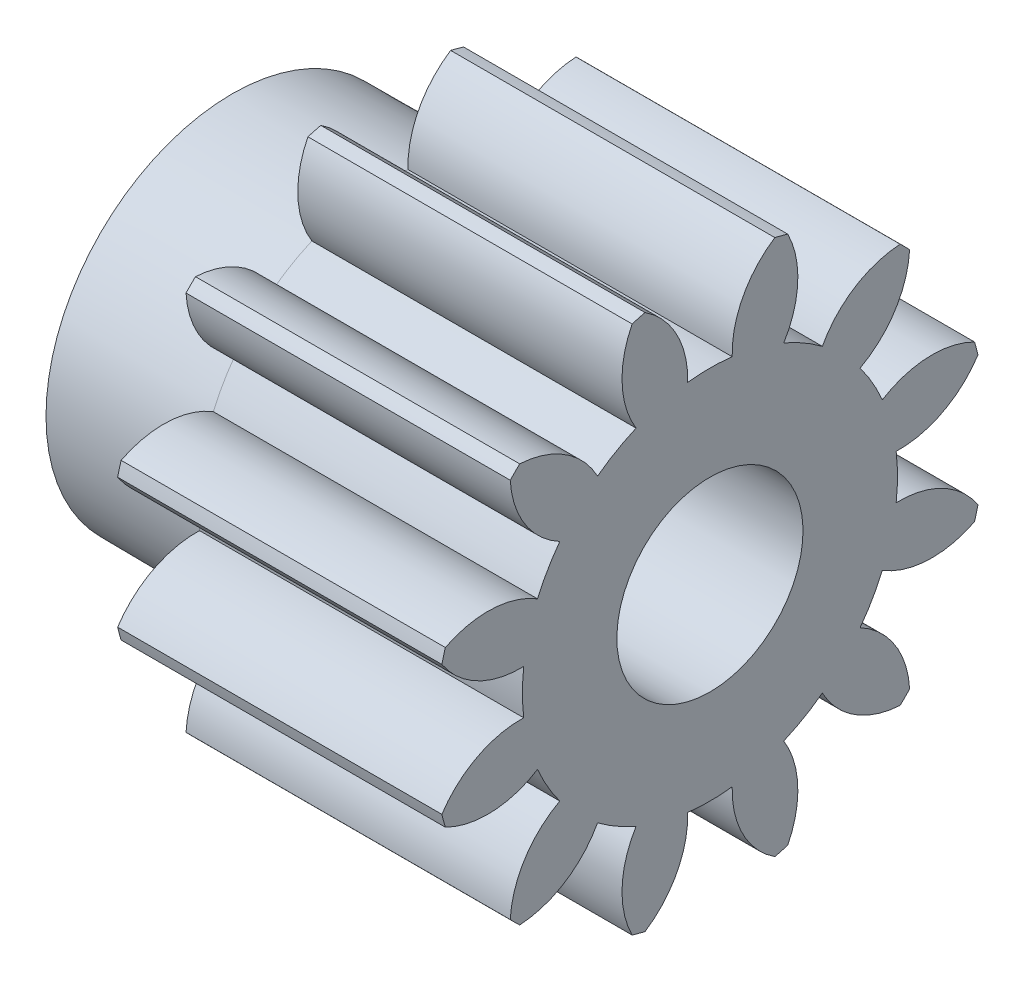
SolidWorks part; units mm, degrees
material "ABS"
ref_plane "Plane1" through (0, 0, 0) normal (0, 0, 1) x (1, 0, 0)
ref_plane "Plane2" through (0, 0, 0) normal (0, 1, 0) x (1, 0, 0)
ref_plane "Plane3" through (0, 0, 0) normal (1, 0, 0) x (0, 0, -1)
sketch "HoldingSke" plane through (0, 0, 0) normal (0, 1, 0) x (1, 0, 0)
  line L0 (0, 0) -> (496.899, -105.6191)
  line L1 (-15, 0) -> (100, 0) construction
  line L2 (0, 0) -> (-2.1039, 2.3779)
  line L3 (0, 0) -> (-11.863, 4.5341)
  line L4 (0, 0) -> (8.4473, 1.7955)
  line L5 (0, 0) -> (-47.5972, -17.7524)
  line L6 (0, 0) -> (-10.5278, -7.1032)
  line L7 (-2.1039, 2.3779) -> (8.8308, 51.9871)
  line L8 (-76.2, 54.61) -> (-69.596, 54.61)
  line L9 (-71.009, 38.7566) -> (-53.1078, 45.2721)
  line L10 (-76.2, 71.12) -> (104.1128, 71.12)
  line L11 (0, 0) -> (-12.7, 0)
  line L12 (-76.2, 101.6) -> (-76.1492, 101.6)
  line L13 (24.9733, 27.94) -> (52.9518, 28.4284)
  line L14 (24.9733, 27.94) -> (25.0241, 27.9398)
  line L15 (24.9733, 27.94) -> (100.4021, 29.52)
  circle A0 centre (0, 0) radius 3.175
  circle A1 centre (0, 0) radius 6.0452
  circle A2 centre (0, 0) radius 38.1
  circle A3 centre (0, 0) radius 3.175
  dimension "Num_teeth" = 12
  dimension "H" = 19.05
  dimension "Pitch_radius" = 180.3128
  dimension "Width" = 12.7
  dimension "Thickness" = 12.7
sketch "BasProSke" plane through (0, 0, 0) normal (0, 1, 0) x (1, 0, 0)
  line L0 (-10, 0) -> (60, 0) construction
  line L1 (0, 0) -> (0, 8.89)
  line L2 (0, 0) -> (12.7, 0)
  line L3 (12.7, 0) -> (12.7, 8.89)
  line L4 (12.7, 8.89) -> (0, 8.89)
  dimension "Thickness" = 12.7
  dimension "Diameter" = 17.78
revolve "Base-Revolve" add sketch "BasProSke" angle 360 about L0
sketch "TooCutSke" plane through (0, 0, 0) normal (1, 0, 0) x (0, 0, -1)
  line L1 (0, 0) -> (0, 107) construction
  line L2 (0, 0) -> (-1.0834, 7.5426) construction
  line L3 (0, 0) -> (-3.9164, 14.6164) construction
  line L4 (-1.0834, 7.5426) -> (-1.9582, 7.3082) construction
  arc A0 (0.7171, 6.0025) -> (-0.7171, 6.0025) centre (0, 0) ccw
  arc A1 (2.1216, 8.6593) -> (-2.1216, 8.6593) centre (0, 0) ccw
  circle A2 centre (0, 0) radius 7.62 construction
  circle A3 centre (0, 0) radius 7.1605 construction
  arc A4 (-0.7171, 6.0025) -> (-2.1216, 8.6593) centre (-3.7638, 6.0915) ccw
  arc A5 (2.1216, 8.6593) -> (0.7171, 6.0025) centre (3.7638, 6.0915) ccw
extrude "ToothCut" cut sketch "TooCutSke" along normal through all
fillet "Breaks" [suppressed] radius 0.0254 tangent propagation no
fillet "RootFillets" [suppressed] radius 0.3048
pattern_circular "TeethCuts" count 12 every 30 about axis through (-10, 0, 0) along (1, 0, 0) of "ToothCut", "RootFillets", "Breaks"
sketch "HubNeaOneSke" plane through (0, 0, 0) normal (-1, 0, 0) x (0, 0, 1)
  circle A0 centre (0, 0) radius 6.0452
  dimension "Diameter" = 12.0904
extrude "HubNearOne" [suppressed] add sketch "HubNeaOneSke" along normal blind 38.1001
sketch "HubNeaBotSke" plane through (0, 0, 0) normal (-1, 0, 0) x (0, 0, 1)
  circle A0 centre (0, 0) radius 6.0452
  dimension "Diameter" = 12.0904
extrude "HubNearBoth" [suppressed] add sketch "HubNeaBotSke" along normal blind 19.05
ref_plane "FarPln" through (12.7, 0, 0) normal (1, 0, 0) x (0, 0, -1)
sketch "HubFarSke" plane through (12.7, 0, 0) normal (1, 0, 0) x (0, 0, -1)
  circle A0 centre (0, 0) radius 6.0452
  dimension "Diameter" = 12.0904
extrude "HubFar" [suppressed] add sketch "HubFarSke" along normal blind 19.05
sketch "BorSke" plane through (0, 0, 0) normal (1, 0, 0) x (0, 0, -1)
  circle A0 centre (0, 0) radius 3
  dimension "D1" = 6
extrude "Bore" cut sketch "BorSke" along normal mid plane 101.6001
sketch "KeySke" plane through (0, 0, 0) normal (1, 0, 0) x (0, 0, -1)
  line L0 (-0.127, 0) -> (-0.127, 3.429)
  line L1 (-0.127, 3.429) -> (0.127, 3.429)
  line L2 (0.127, 3.429) -> (0.127, 0)
  line L3 (0, 0) -> (0, 34) construction
  line L4 (-0.127, 0) -> (0.127, 0)
  dimension "Width" = 0.254
extrude "Keyway" [suppressed] cut sketch "KeySke" along normal mid plane 101.6001
pattern_circular "Keyway2" [suppressed] count 2 every 90 about axis through (-10, 0, 0) along (1, 0, 0) reverse direction yes
sketch "Sketch1" plane through (0, 0, 0) normal (0, 0, 1) x (1, 0, 0)
  line L0 (0, 0) -> (-2.5422, 0) construction
  line L1 (0, -4) -> (-4.95, -4)
  line L2 (-4.95, -4) -> (-4.95, -6)
  line L3 (-4.95, -6) -> (0, -6.0452)
  line L4 (0, -6.0452) -> (0, -4)
  dimension "D1" = 2
  dimension "D2" = 4
  dimension "D3" = 4.95
revolve "Revolve1" add sketch "Sketch1" angle 360 about L0
sketch "Sketch2" plane through (0, 0, 0) normal (0, 0, 1) x (1, 0, 0)
  line L0 (12.7, -8.6403) -> (0, -8.6403) construction
  line L1 (12.7, 8.6403) -> (10.45, 8.6403)
  line L2 (12.7, 8.6403) -> (12.7, -8.6403)
  line L3 (12.7, -8.6403) -> (10.45, -8.6403)
  line L4 (10.45, 8.6403) -> (10.45, -8.6403)
  dimension "D1" = 2.25
extrude "Cut-Extrude1" cut sketch "Sketch2" against normal through all both and the other way through all
ref_axis "Axis1" through (-5.8156, 0, 0) along (1, 0, 0)
equation "' \"Pitch@HoldingSke\" = 4"
equation "' \"Num_teeth@HoldingSke\" = 12"
equation "' \"Ap@HoldingSke\" =  20"
equation "' \"Ap@HoldingSke\" = 20"
equation "' \"Width@HoldingSke\" = 0.5"
equation "' \"Hub_dia@HoldingSke\"= 1"
equation "' \"Hub_dia@HoldingSke\" = 1"
equation "' \"Overall_len@HoldingSke\" = 1.0"
equation "' \"Bore@HoldingSke\" = 0.75"
equation "' \"T_dim@HoldingSke\" = 0.85"
equation "' \"Width@KeySke\" = 0.25"
equation "' \"Show_teeth@HoldingSke\" = 13"
equation "' \"Backlash@HoldingSke\" = 0.009"
equation "' \"Addendum_fac@HoldingSke\" = 1.0"
equation "' \"Dedendum_fac@HoldingSke\" = 1.25"
equation "' \"Dedendum_add@HoldingSke\" = 0.00005"
equation "' \"Clearance_fac@HoldingSke\" = 0.25"
equation "' \"Pitch@HoldingSke\" = 0.5"
equation "' \"Num_teeth@HoldingSke\" = 23"
equation "' \"Show_teeth@HoldingSke\" = 23"
equation "' \"Backlash@HoldingSke\" = 0.0375"
equation "\"Overcut_dia@TooCutSke\" = (\"Num_teeth@HoldingSke\" + 2 * \"Addendum_fac@HoldingSke\") / \"Pitch@HoldingSke\" + 0.002"
equation "\"Pitch_dia@TooCutSke\" = \"Num_teeth@HoldingSke\" / \"Pitch@HoldingSke\""
equation "\"Base_dia@TooCutSke\" = \"Num_teeth@HoldingSke\" / \"Pitch@HoldingSke\" * cos((\"Ap@HoldingSke\"  * 3.14159265 / 180))"
equation "\"Root_dia@TooCutSke\" = (\"Num_teeth@HoldingSke\" + 2) / \"Pitch@HoldingSke\" - 2 * (\"Addendum_fac@HoldingSke\" + \"Dedendum_fac@HoldingSke\") / \"Pitch@HoldingSke\" - \"Dedendum_add@HoldingSke\" * 2"
equation "\"Half_ang@TooCutSke\" = 180 / \"Num_teeth@HoldingSke\""
equation "\"Half_CT@TooCutSke\" = \"Num_teeth@HoldingSke\" / \"Pitch@HoldingSke\" * sin((3.14159265 / 2 / \"Num_teeth@HoldingSke\")) / 2 - 7 * \"Backlash@HoldingSke\" / 4"
equation "\"Flank_rad@TooCutSke\" = \"Num_teeth@HoldingSke\" / \"Pitch@HoldingSke\" / 5"
equation "\"Radius@RootFillets\" = \"Clearance_fac@HoldingSke\" / \"Pitch@HoldingSke\" + \"Dedendum_add@HoldingSke\""
equation "\"Break_rad@Breaks\" = 0.02 / \"Pitch@HoldingSke\""
equation "\"Thickness@HoldingSke\" = \"Width@HoldingSke\""
equation "\"OAL@HoldingSke\" = \"Thickness@HoldingSke\""
equation "\"MHD@HoldingSke\" = (\"Num_teeth@HoldingSke\" + 2) / \"Pitch@HoldingSke\" - 2 * (\"Addendum_fac@HoldingSke\" + \"Dedendum_fac@HoldingSke\")  / \"Pitch@HoldingSke\" - \"Dedendum_add@HoldingSke\" * 2"
equation "\"MBD@HoldingSke\" = (\"Num_teeth@HoldingSke\" + 2) / \"Pitch@HoldingSke\" - 2 * (\"Addendum_fac@HoldingSke\" + \"Dedendum_fac@HoldingSke\")  / \"Pitch@HoldingSke\" - \"Dedendum_add@HoldingSke\" * 2 - 0.002"
equation "\"MHD@HoldingSke\" = ((sgn( \"MHD@HoldingSke\" - \"Hub_dia@HoldingSke\" )-1)*( \"MHD@HoldingSke\" - \"Hub_dia@HoldingSke\" ))/-2+ \"Hub_dia@HoldingSke\""
equation "\"MBD@HoldingSke\" = ((sgn( \"MBD@HoldingSke\" - \"Bore@HoldingSke\" )-1)*( \"MBD@HoldingSke\" - \"Bore@HoldingSke\" ))/-2+ \"Bore@HoldingSke\""
equation "\"OAL@HoldingSke\" = ((sgn( \"OAL@HoldingSke\" - \"Overall_len@HoldingSke\" )+1)*( \"OAL@HoldingSke\" - \"Overall_len@HoldingSke\" ))/2 + \"Overall_len@HoldingSke\" + 0.000002"
equation "\"Num_teeth@TeethCuts\" = int( \"Show_teeth@HoldingSke\" ) + 1"
equation "\"Num_teeth@TeethCuts\" = ((sgn( \"Num_teeth@TeethCuts\" - \"Num_teeth@HoldingSke\" )-1)*( \"Num_teeth@TeethCuts\" - \"Num_teeth@HoldingSke\" ))/-2+ \"Num_teeth@HoldingSke\""
equation "\"Num_teeth@TeethCuts\" = ((sgn( \"Num_teeth@TeethCuts\" - 2.0)+1)*( \"Num_teeth@TeethCuts\" - 2.0))/2 +2.0"
equation "\"Angle@TeethCuts\" = 360.0 / \"Num_teeth@HoldingSke\""
equation "\"Diameter@BasProSke\" = (\"Num_teeth@HoldingSke\" + 2 * \"Addendum_fac@HoldingSke\") / \"Pitch@HoldingSke\""
equation "\"Thickness@BasProSke\"  = \"Thickness@HoldingSke\""
equation "' \"Fillet_rad@BasProSke\" =  \"Thickness@HoldingSke\" * 0.05"
equation "' \"Fillet_rad@BasProSke\" = \"Thickness@HoldingSke\" * 0.05"
equation "\"MHD@HoldingSke\" = ((sgn( \"MHD@HoldingSke\" - \"Root_dia@TooCutSke\" )-1)*( \"MHD@HoldingSke\" - \"Root_dia@TooCutSke\" ))/-2+ \"Root_dia@TooCutSke\""
equation "\"Diameter@HubNeaOneSke\" = \"MHD@HoldingSke\""
equation "\"Length@HubNearOne\" = \"OAL@HoldingSke\" - \"Thickness@BasProSke\""
equation "\"Diameter@HubNeaBotSke\" = \"MHD@HoldingSke\""
equation "\"Length@HubNearBoth\" = ( \"OAL@HoldingSke\" - \"Thickness@BasProSke\" ) / 2.0"
equation "\"Thickness@FarPln\" = \"Thickness@BasProSke\""
equation "\"Diameter@HubFarSke\" = \"MHD@HoldingSke\""
equation "\"Length@HubFar\" = ( \"OAL@HoldingSke\" - \"Thickness@BasProSke\" ) / 2.0"
equation "\"D1@Bore\" = \"OAL@HoldingSke\" * 2.0"
equation "\"D1@Keyway\" = \"OAL@HoldingSke\" * 2.0"
equation "\"Offset@KeySke\" = \"T_dim@HoldingSke\" - \"MBD@HoldingSke\" / 2.0"
